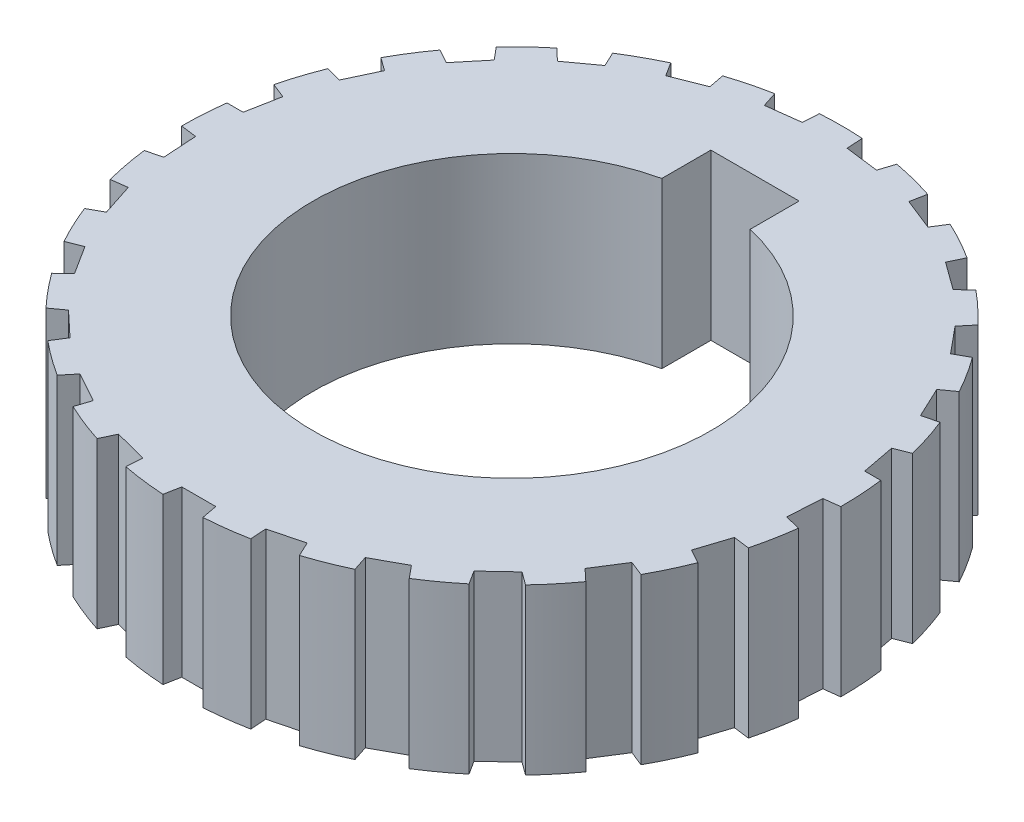
SolidWorks part; units mm, degrees
ref_plane "Front Plane" through (0, 0, 0) normal (0, 0, 1) x (1, 0, 0)
ref_plane "Top Plane" through (0, 0, 0) normal (0, 1, 0) x (1, 0, 0)
ref_plane "Right Plane" through (0, 0, 0) normal (1, 0, 0) x (0, 0, -1)
sketch "Sketch1" plane through (0, 0, 0) normal (0, 1, 0) x (1, 0, 0)
  circle A0 centre (0, 0) radius 38.1
extrude "Boss-Extrude1" add sketch "Sketch1" along normal blind 19.05
sketch "Sketch2" plane through (0, 0, 0) normal (0, -1, 0) x (1, 0, 0)
  line L6 (-1.9657, 36.2) -> (1.9657, 36.2)
  line L7 (2.3241, 38.105) -> (1.9657, 36.2)
  line L8 (-2.3241, 38.105) -> (-1.9657, 36.2)
  line L9 (-2.3241, 38.105) -> (2.3241, 38.105)
  dimension "D1" = 1.905
  dimension "D2" = 36.2
extrude "Cut-Extrude1" cut sketch "Sketch2" against normal blind 33
pattern_circular "CirPattern1" count 25 over 360 about axis through (0, 0, 0) along (0, 1, 0) of "Cut-Extrude1"
sketch "Sketch3" plane through (0, 19.05, 0) normal (0, 1, 0) x (1, 0, 0)
  line L0 (0, 23) -> (5.1, 23)
  line L1 (0, 23) -> (-5.1, 23)
  line L2 (-5.1, 23) -> (-5.1, 22.4274)
  line L3 (5.1, 23) -> (5.1, 22.4274)
  line L7 (5.1, 23) -> (5.1, 28.1)
  line L8 (5.1, 28.1) -> (-5.1, 28.1)
  line L9 (-5.1, 28.1) -> (-5.1, 23)
  circle A0 centre (0, 0) radius 23
  dimension "D1" = 10.2
extrude "Cut-Extrude2" cut sketch "Sketch3" against normal blind 25.4 contours A0 | A0 | A0 L1 L2 | A0 L3 L0 | L8 L9 L1 L0 L7 region at (0, 19.05, -25.55) region at (-3.8282, 19.05, -22.8286) region at (3.8282, 19.05, -22.8286) region at (0, 19.05, 0)
